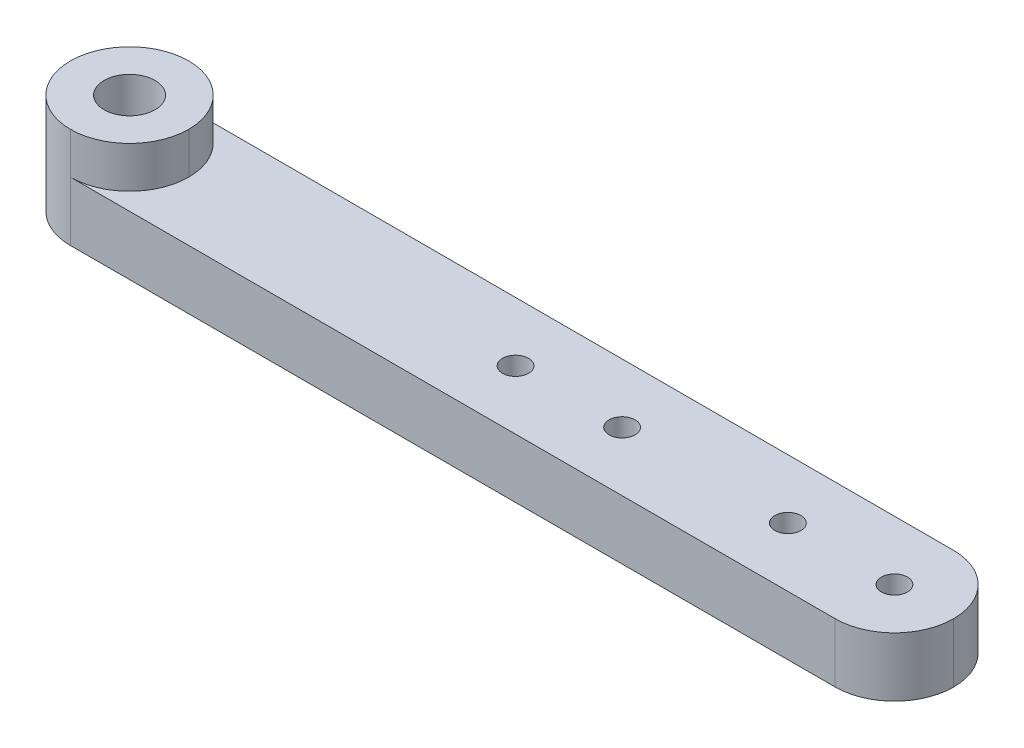
SolidWorks part; units mm, degrees
ref_plane "정면" through (0, 0, 0) normal (0, 0, 1) x (1, 0, 0)
ref_plane "윗면" through (0, 0, 0) normal (0, 1, 0) x (1, 0, 0)
ref_plane "우측면" through (0, 0, 0) normal (1, 0, 0) x (0, 0, -1)
sketch "스케치1" plane through (0, 0, 0) normal (0, 0, 1) x (1, 0, 0)
  line L1 (-37.3, -2.5) -> (37.3, -2.5)
  line L2 (-37.3, -2.5) -> (-37.3, 2.5)
  line L3 (-37.3, 2.5) -> (37.3, 2.5)
  line L4 (37.3, -2.5) -> (37.3, 2.5)
  line L5 (-37.3, -2.5) -> (37.3, 2.5) construction
  line L6 (-37.3, 2.5) -> (37.3, -2.5) construction
  point P0 (0, 0)
  dimension "D1" = 74.6
  dimension "D2" = 5
extrude "보스-돌출1" add sketch "스케치1" along normal blind 10
sketch "스케치4" plane through (0, 2.5, 0) normal (0, 1, 0) x (1, 0, 0)
  line L0 (37.3, 0) -> (-37.3, 0) construction
  line L1 (-27.3, 0) -> (-37.3, 0)
  line L2 (-27.3, 0) -> (-27.3, -10)
  line L3 (-27.3, -10) -> (-37.3, -10)
  line L4 (-37.3, 0) -> (-37.3, -10)
  line L5 (-37.3, -10) -> (-37.3, 0) construction
  dimension "D1" = 10
extrude "보스-돌출2" add sketch "스케치4" along normal blind 3.5
fillet "필렛1" radius 5 6 edges at (37.3, 0, 10) (37.3, 0, 0) (-37.3, 1.75, 0) (-37.3, 1.75, 10) (-27.3, 4.25, 10) (-27.3, 4.25, 0)
sketch "스케치2" plane through (0, 6, 0) normal (0, 1, 0) x (1, 0, 0)
  line L0 (23.3, -5) -> (32.3, -5) construction
  line L1 (0.3, -5) -> (9.3, -5) construction
  circle A0 centre (-32.3, -5) radius 2.15
  circle A1 centre (32.3, -5) radius 1.1
  circle A3 centre (23.3, -5) radius 1.1
  circle A5 centre (9.3, -5) radius 1.1
  circle A7 centre (0.3, -5) radius 1.1
  dimension "D1" = 4.3
  dimension "D2" = 2.2
  dimension "D3" = 9
  dimension "D4" = 9
  dimension "D9" = 2.2
  dimension "D10" = 14
extrude "컷-돌출1" cut sketch "스케치2" against normal through all
